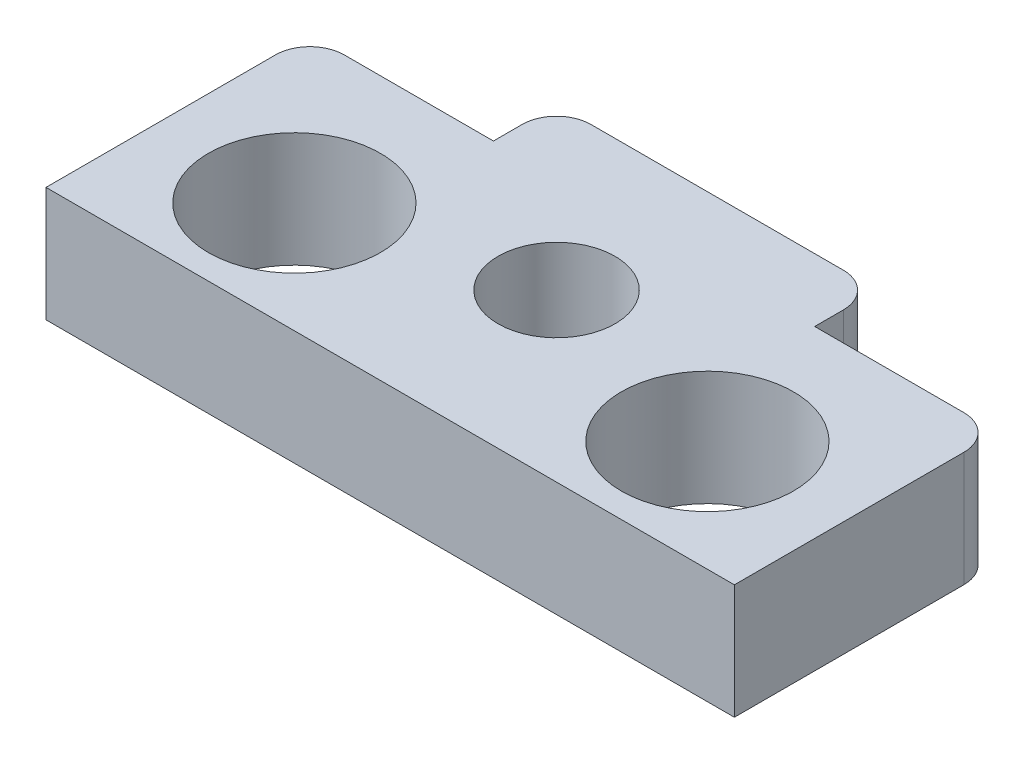
SolidWorks part; units mm, degrees
ref_plane "前视基准面" through (0, 0, 0) normal (0, 0, 1) x (1, 0, 0)
ref_plane "上视基准面" through (0, 0, 0) normal (0, 1, 0) x (1, 0, 0)
ref_plane "右视基准面" through (0, 0, 0) normal (1, 0, 0) x (0, 0, -1)
sketch "草图1" plane through (0, 0, 0) normal (0, 1, 0) x (1, 0, 0)
  line L1 (0, 0) -> (0, -15) construction
  line L2 (0, 0) -> (-30, 0)
  line L4 (-30, 0) -> (-30, 23)
  line L5 (-30, 23) -> (-14, 23)
  line L6 (-14, 23) -> (-14, 28.5)
  line L13 (-14, 28.5) -> (14, 28.5)
  line L14 (14, 28.5) -> (14, 23)
  line L15 (14, 23) -> (30, 23)
  line L16 (30, 23) -> (30, 0)
  line L17 (30, 0) -> (0, 0)
  point P0 (0, 0)
  dimension "D1" = 30
  dimension "D2" = 5.5
  dimension "D3" = 23
  dimension "D4" = 16
extrude "凸台-拉伸1" add sketch "草图1" along normal blind 10
sketch "草图3" plane through (0, 10, 0) normal (0, 1, 0) x (1, 0, 0)
  line L1 (0, 0) -> (0, 28.5) construction
  line L2 (14, 28.5) -> (-14, 28.5) construction
  line L3 (-30, 0) -> (30, 0) construction
  circle A0 centre (0, 14.5) radius 5.1
  circle A1 centre (-18, 9.65) radius 7.5
  circle A2 centre (18, 9.65) radius 7.5
  dimension "D1" = 10.2
  dimension "D2" = 14
  dimension "D3" = 15
  dimension "D4" = 36
  dimension "D5" = 9.65
extrude "切除-拉伸2" cut sketch "草图3" against normal through all
fillet "圆角2" radius 3 4 edges at (30, 5, -23) (14, 5, -28.5) (-14, 5, -28.5) (-30, 5, -23)
